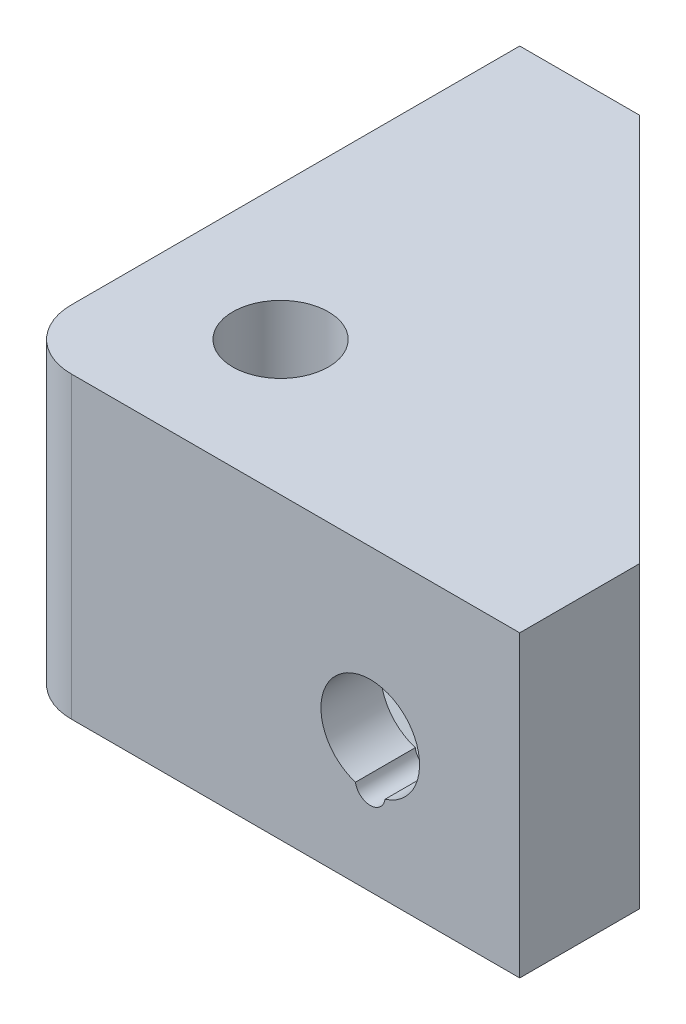
SolidWorks part; units mm, degrees
material "PET"
ref_plane "Front Plane" through (0, 0, 0) normal (0, 0, 1) x (1, 0, 0)
ref_plane "Top Plane" through (0, 0, 0) normal (0, 1, 0) x (1, 0, 0)
ref_plane "Right Plane" through (0, 0, 0) normal (1, 0, 0) x (0, 0, -1)
sketch "Sketch1" plane through (0, 0, 0) normal (0, 1, 0) x (1, 0, 0)
  line L2 (10.5, 10.5) -> (17, 4)
  line L3 (17, 4) -> (17, 0)
  line L4 (17, 0) -> (0, 0)
  line L5 (0, 0) -> (10.5, 10.5)
  dimension "D1" = 45
  dimension "D2" = 17
  dimension "D3" = 4
extrude "Boss-Extrude1" add sketch "Sketch1" along normal blind 10
sketch "Sketch4" plane through (0, 0, 0) normal (0, 0, 1) x (1, 0, 0)
  line L0 (0, 10) -> (17, 10) construction
  line L1 (17, 10) -> (17, 0) construction
  arc A0 (12.4945, 2.9258) -> (11.5055, 2.9258) centre (12, 4.5) ccw
  arc A1 (11.5055, 2.9258) -> (12.4945, 2.9258) centre (12, 3) ccw
  point P2 (0, 0)
  point P10 (12, 4.5)
  dimension "D1" = 3.3
  dimension "D3" = 1
  dimension "D4" = 0.15
  dimension "D2" = 5.5
  dimension "D5" = 5
extrude "Cut-Extrude2" cut sketch "Sketch4" against normal through all
sketch "Sketch6" plane through (0, 10, 0) normal (0, 1, 0) x (1, 0, 0)
  line L3 (0, 0) -> (17, 0) construction
  line L5 (10.5, 10.5) -> (0, 0) construction
  circle A0 centre (4.5, 4.5) radius 1.6
  dimension "D3" = 3.2
  dimension "D4" = 4.5
extrude "Cut-Extrude3" cut sketch "Sketch6" against normal through all
sketch "Sketch9" plane through (0, 0, 0) normal (0, -1, 0) x (1, 0, 0)
  line L0 (3.3686, -3.3686) -> (0, 0) construction
  line L1 (7.5393, -5.3144) -> (6.725, -2.275)
  line L2 (6.725, -2.275) -> (3.6856, -1.4607)
  line L3 (3.6856, -1.4607) -> (1.4607, -3.6856)
  line L4 (1.4607, -3.6856) -> (2.275, -6.725)
  line L5 (2.275, -6.725) -> (5.3144, -7.5393)
  line L6 (5.3144, -7.5393) -> (7.5393, -5.3144)
  circle A0 centre (4.5, -4.5) radius 2.725 construction
  dimension "D1" = 5.45
extrude "Cut-Extrude4" cut sketch "Sketch9" against normal blind 4
fillet "Fillet3" radius 1 4 edges at (3.1294, 0, -2.0169) (5.2053, 0, -1.8679) (7.1321, 0, -3.7947) (6.9831, 0, -5.8706)
sketch "Sketch10" plane through (0, 0, 0) normal (0, 0, 1) x (1, 0, 0)
  line L1 (12, 1.3246) -> (14.75, 2.9123)
  line L2 (14.75, 2.9123) -> (14.75, 6.0877)
  line L3 (14.75, 6.0877) -> (12, 7.6754)
  line L4 (12, 7.6754) -> (9.25, 6.0877)
  line L5 (9.25, 6.0877) -> (9.25, 2.9123)
  line L6 (9.25, 2.9123) -> (12, 1.3246)
  circle A0 centre (12, 4.5) radius 2.75 construction
  dimension "D1" = 5.5
extrude "Cut-Extrude5" cut sketch "Sketch10" against normal through all from offset 2 offset against normal yes
mirror "Mirror1" about plane through (0, 10, 0) normal (0.7071, 0, 0.7071) of bodies 108 103
fillet "Fillet1" radius 2 1 edges at (0, 5, 0)
fillet "Fillet6" radius 1 13 edges at (7.625, 2.1184, -13.375) (6.25, 4.5, -14.75) (7.625, 6.8816, -13.375) (9.75, 7.2424, -11.25) (13.375, 6.8816, -7.625) (14.75, 4.5, -6.25) (13.375, 2.1184, -7.625) (11.25, 1.7576, -9.75) (9.75, 1.7576, -11.25) (11.25, 7.2424, -9.75) (9.875, 2.5514, -9.875) (9.875, 6.4486, -9.875) (9.25, 4.5, -9.25)
